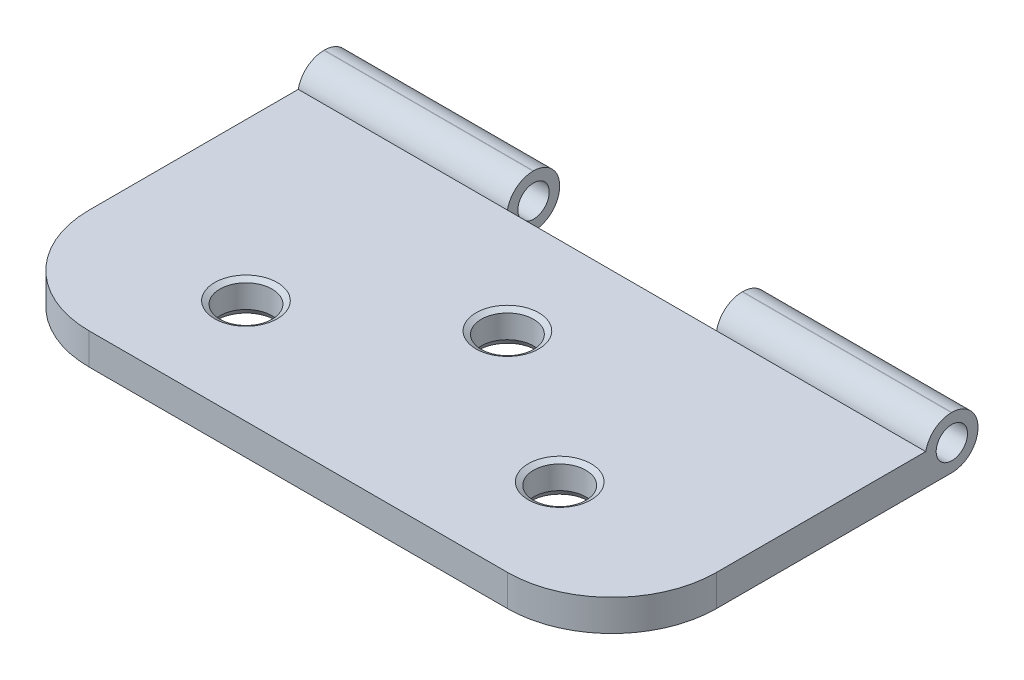
SolidWorks part; units mm, degrees
ref_plane "Front Plane" through (0, 0, 0) normal (0, 0, 1) x (1, 0, 0)
ref_plane "Top Plane" through (0, 0, 0) normal (0, 1, 0) x (1, 0, 0)
ref_plane "Right Plane" through (0, 0, 0) normal (1, 0, 0) x (0, 0, -1)
sketch "Szkic1" plane through (0, 0, 0) normal (0, 1, 0) x (1, 0, 0)
  line L1 (-30, 15) -> (30, 15)
  line L2 (-30, 15) -> (-30, -15)
  line L3 (-30, -15) -> (30, -15)
  line L4 (30, 15) -> (30, -15)
  line L5 (-30, 15) -> (30, -15) construction
  line L6 (-30, -15) -> (30, 15) construction
  point P0 (0, 0)
  dimension "D1" = 60
  dimension "D2" = 30
extrude "Dodanie-wyciągnięcie1" add sketch "Szkic1" along normal blind 3
sketch "Szkic2" plane through (0, 3, 0) normal (0, 1, 0) x (1, 0, 0)
  line L0 (0, 15) -> (0, 5) construction
  line L1 (30, 15) -> (-30, 15) construction
  line L2 (0, -15) -> (0, -5) construction
  line L3 (-30, -15) -> (30, -15) construction
  line L4 (0, -5) -> (30, -5) construction
  line L5 (30, -15) -> (30, 15) construction
  line L6 (0, -5) -> (-30, -5) construction
  line L7 (-30, 15) -> (-30, -15) construction
  circle A0 centre (-15, -5) radius 2.5
  circle A1 centre (15, -5) radius 2.5
  circle A2 centre (0, 5) radius 2.5
  dimension "D1" = 5
  dimension "D2" = 5
  dimension "D3" = 5
extrude "Wytnij-wyciągnięcie1" cut sketch "Szkic2" against normal blind 5
sketch "Szkic4" plane through (0, 0, -15) normal (0, 0, -1) x (-1, 0, 0)
  line L0 (-30, 3) -> (30, 3) construction
  line L1 (-30, 0) -> (-10, 0)
  line L2 (-30, 0) -> (-30, 3)
  line L3 (-30, 3) -> (-10, 3)
  line L4 (-10, 0) -> (-10, 3)
  line L6 (30, 0) -> (10, 0)
  line L7 (30, 0) -> (30, 3)
  line L8 (30, 3) -> (10, 3)
  line L9 (10, 0) -> (10, 3)
  dimension "D1" = 20
  dimension "D2" = 20
extrude "Dodanie-wyciągnięcie2" add sketch "Szkic4" along normal blind 5
sketch "Szkic5" plane through (0, 3, 0) normal (0, 1, 0) x (1, 0, 0)
  line L0 (30, -15) -> (30, 20) construction
  line L1 (-30, 20) -> (-10, 20)
  line L2 (-30, 20) -> (-30, 15)
  line L3 (-30, 15) -> (-10, 15)
  line L4 (-10, 20) -> (-10, 15)
  line L5 (10, 20) -> (30, 20)
  line L6 (10, 20) -> (10, 15)
  line L7 (10, 15) -> (30, 15)
  line L8 (30, 20) -> (30, 15)
extrude "Dodanie-wyciągnięcie3" add sketch "Szkic5" along normal blind 2
fillet "Zaokrąglenie1" radius 2.5 6 edges at (-20, 0, -20) (-20, 5, -15) (-20, 5, -20) (20, 0, -20) (20, 5, -20) (20, 5, -15)
sketch "Szkic6" plane through (30, 0, 0) normal (1, 0, 0) x (0, 0, -1)
  line L0 (17.5, 5) -> (17.5, 0) construction
  circle A0 centre (17.5, 2.5) radius 1.5
  dimension "D1" = 3
extrude "Wytnij-wyciągnięcie2" cut sketch "Szkic6" against normal blind 60
fillet "Zaokrąglenie2" radius 10 2 edges at (30, 1.5, 15) (-30, 1.5, 15)
chamfer "Sfazowanie1" distance 0.5 angle 30 6 edges at (15, 0, 7.5) (-15, 0, 7.5) (0, 0, -2.5) (-15, 3, 7.5) (0, 3, -2.5) (15, 3, 7.5) first distance on face at (15, 3, 7.5) first distance on face at (-15, 3, 7.5) first distance on face at (0, 3, -2.5)
